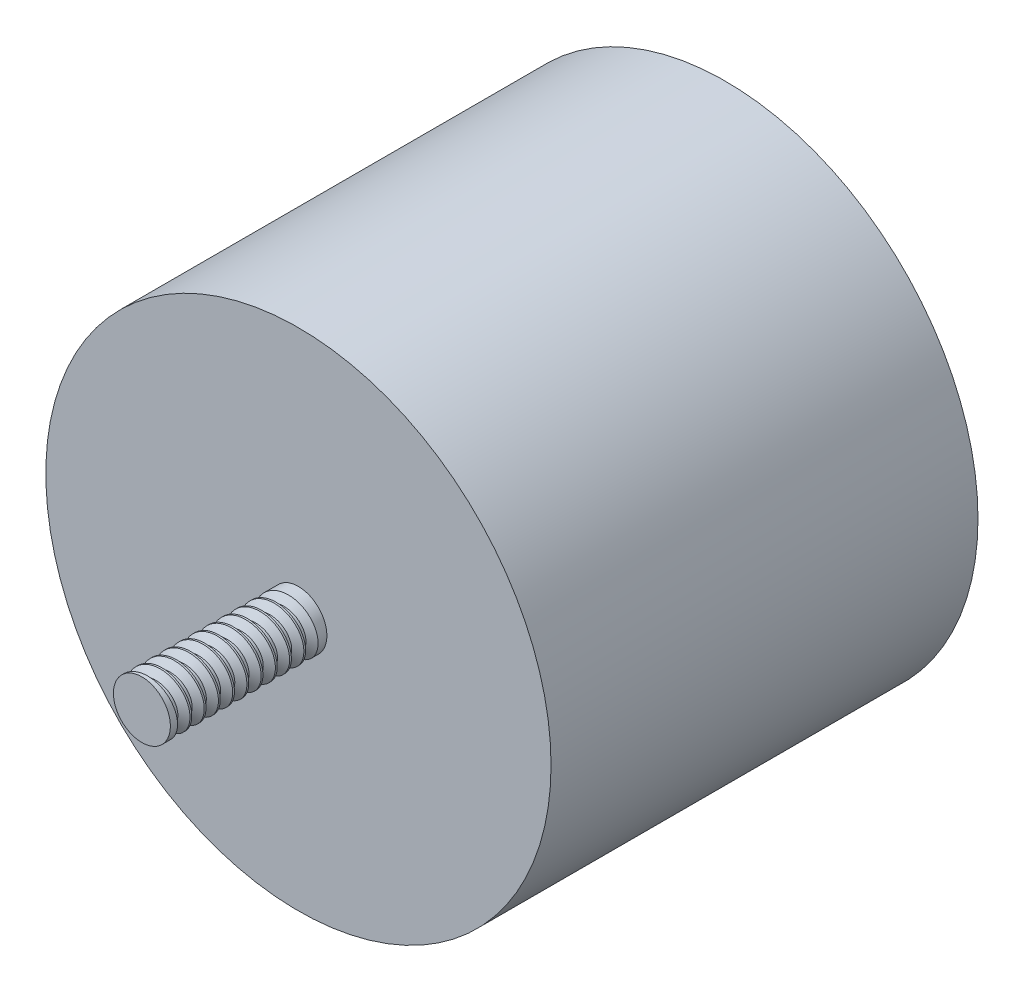
SolidWorks part; units mm, degrees
material "Nickel"
ref_plane "Front Plane" through (0, 0, 0) normal (0, 0, 1) x (1, 0, 0)
ref_plane "Top Plane" through (0, 0, 0) normal (0, 1, 0) x (1, 0, 0)
ref_plane "Right Plane" through (0, 0, 0) normal (1, 0, 0) x (0, 0, -1)
sketch "Sketch2" plane through (0, 0, 0) normal (0, 0, 1) x (1, 0, 0)
  circle A0 centre (0, 0) radius 17.75
  dimension "D1" = 35.5
extrude "Boss-Extrude1" add sketch "Sketch2" along normal blind 30
sketch "Sketch3" plane through (0, 0, 30) normal (0, 0, 1) x (1, 0, 0)
  circle A0 centre (0, 0) radius 2
  dimension "D1" = 4
extrude "Boss-Extrude2" add sketch "Sketch3" along normal blind 11
thread "Thread1" pitch 1 method cut profile "Thread Profile1" start angle 0, offset 0, length 10, pitch 1, diameter 4
ref_plane "Plane1" through (-2, 0, 41) normal (0, -1, 0) x (-1, 0, 0)
sketch "Thread Profile1" plane through (-2, 0, 41) normal (0, -1, 0) x (-1, 0, 0)
  line L0 (0, 0) -> (0, 1) construction
  line L11 (0, 0) -> (0, 0.875)
  line L12 (0, 0.875) -> (-0.5413, 0.5625)
  line L13 (-0.5413, 0.5625) -> (-0.5413, 0.3125)
  line L15 (-0.5413, 0.3125) -> (0, 0)
  line L17 (-0.5413, 0.4375) -> (0, 0.4375) construction
  point P2 (0, 0)
  dimension "Pitch" = 1
  dimension "Profile_Angle" = 60
  dimension "Profile_Land" = 0.25
  dimension "Profile_Height" = 0.5413
